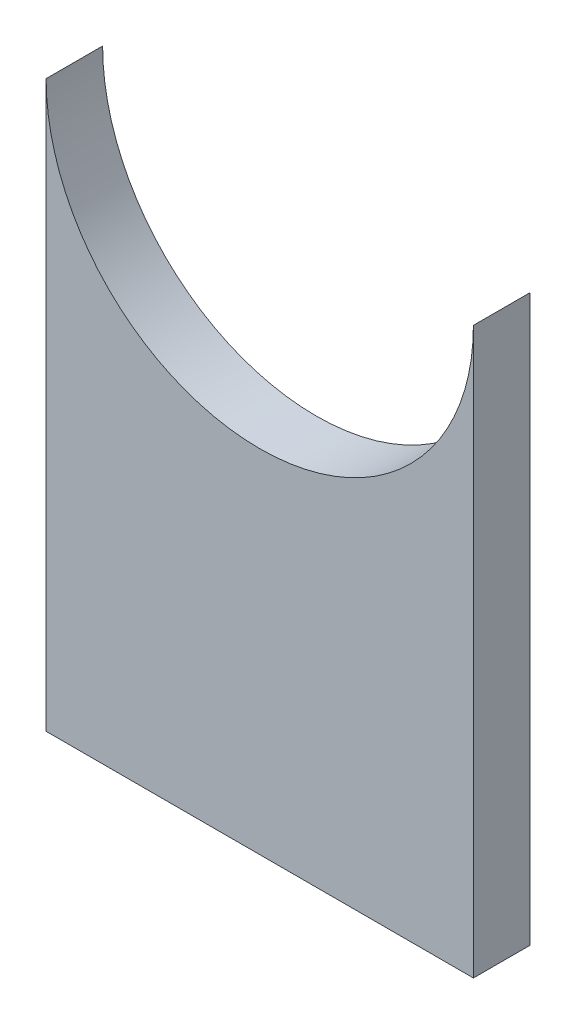
SolidWorks part; units mm, degrees
ref_plane "Front Plane" through (0, 0, 0) normal (0, 0, 1) x (1, 0, 0)
ref_plane "Top Plane" through (0, 0, 0) normal (0, 1, 0) x (1, 0, 0)
ref_plane "Right Plane" through (0, 0, 0) normal (1, 0, 0) x (0, 0, -1)
sketch "Sketch1" plane through (0, 0, 0) normal (0, 0, 1) x (1, 0, 0)
  line L0 (0, -63.5) -> (0, 36.9747) construction
  line L1 (-24.003, -63.5) -> (24.003, -63.5)
  line L2 (-24.003, -63.5) -> (-24.003, 0)
  line L4 (24.003, -63.5) -> (24.003, 0)
  line L5 (-24.003, -63.5) -> (24.003, 0) construction
  line L6 (-24.003, 0) -> (24.003, -63.5) construction
  line L7 (1.27, -50.8) -> (27.5942, -50.8) construction
  arc A0 (-24.003, 0) -> (24.003, 0) centre (0, 0) ccw
  point P3 (0, -31.75)
  dimension "D1" = 63.5
  dimension "D3" = 24.003
  dimension "D2" = 12.7
extrude "Boss-Extrude1" add sketch "Sketch1" along normal blind 6.35
sketch "Sketch2" plane through (0, 0, 0) normal (0, 1, 0) x (1, 0, 0)
  line L3 (24.003, -3.175) -> (-24.003, -3.175) construction
  line L4 (24.003, -6.35) -> (24.003, 0) construction
  line L5 (-24.003, -6.35) -> (-24.003, 0) construction
  point P0 (0, -3.175)
  point P7 (0, -3.175)
